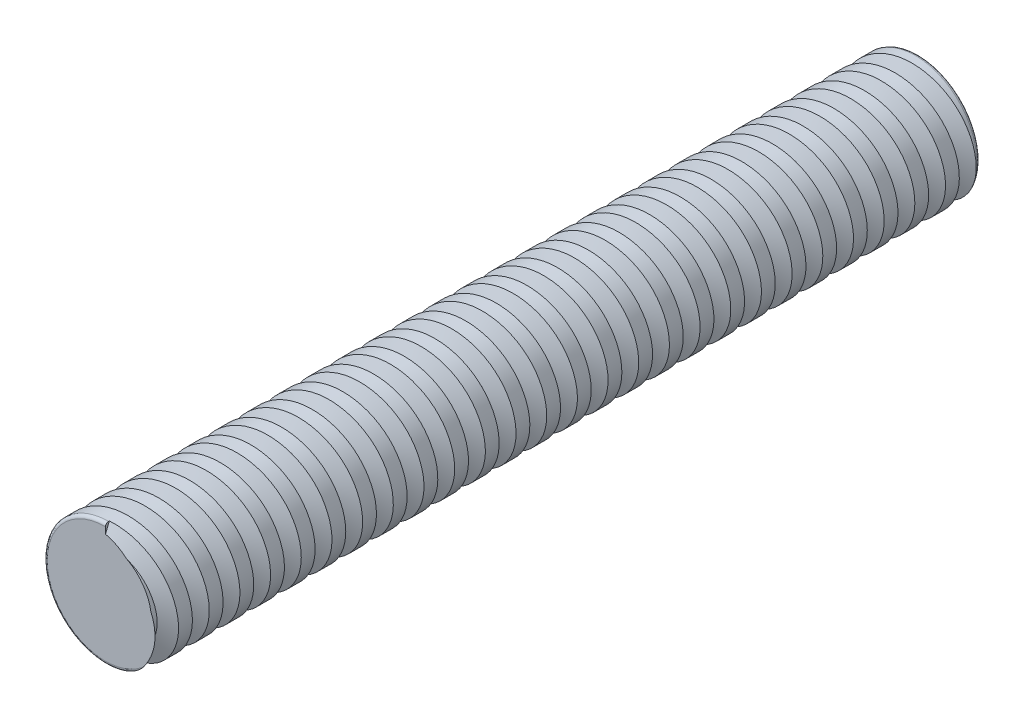
SolidWorks part; units mm, degrees
ref_plane "Front Plane" through (0, 0, 0) normal (0, 0, 1) x (1, 0, 0)
ref_plane "Top Plane" through (0, 0, 0) normal (0, 1, 0) x (1, 0, 0)
ref_plane "Right Plane" through (0, 0, 0) normal (1, 0, 0) x (0, 0, -1)
sketch "Sketch1" plane through (0, 0, 0) normal (0, 0, 1) x (1, 0, 0)
  circle A0 centre (0, 0) radius 4
  dimension "D1" = 8
extrude "Boss-Extrude1" add sketch "Sketch1" against normal blind 53
fillet "Fillet1" radius 0.2 2 edges at (4, 0, -53) (4, 0, 0)
sketch "Sketch2" plane through (0, 0, 0) normal (0, 0, 1) x (1, 0, 0)
  circle A0 centre (0, 0) radius 4
  dimension "D1" = 8
sketch "Sketch3" plane through (0, 0, 0) normal (0, 1, 0) x (1, 0, 0)
  line L0 (3, 0.35) -> (3, 0.05)
  line L1 (3, 0.05) -> (5, -0.75)
  line L2 (5, -0.75) -> (5, 1.15)
  line L3 (5, 1.15) -> (3, 0.35)
  line L4 (5, 0.2) -> (3, 0.2)
  line L7 (4, 0.2) -> (-4, 0.2) construction
  point P7 (4, 0.2)
  dimension "D1" = 1.9
  dimension "D2" = 2
  dimension "D3" = 0.3
  dimension "D4" = 4
curve "Helix/Spiral1" pitch 2 height 200 turns 100
sweep "Cut-Sweep1" cut profiles "Sketch3" path "Helix/Spiral1"
